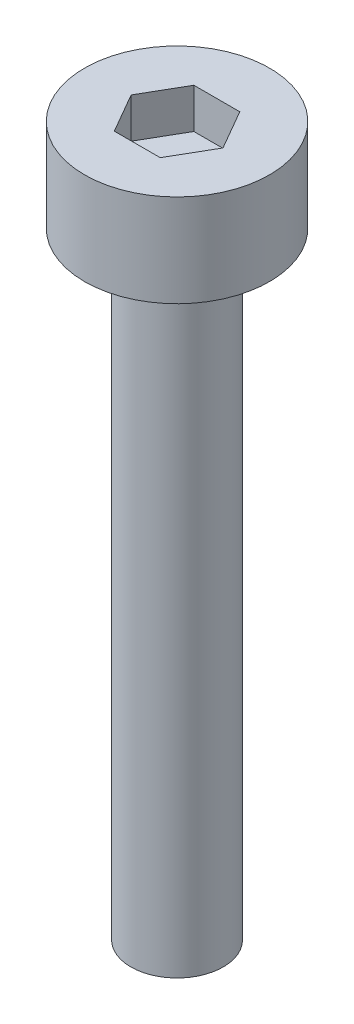
SolidWorks part; units mm, degrees
ref_plane "Front Plane" through (0, 0, 0) normal (0, 0, 1) x (1, 0, 0)
ref_plane "Top Plane" through (0, 0, 0) normal (0, 1, 0) x (1, 0, 0)
ref_plane "Right Plane" through (0, 0, 0) normal (1, 0, 0) x (0, 0, -1)
sketch "Sketch1" plane through (0, 0, 0) normal (0, 1, 0) x (1, 0, 0)
  circle A0 centre (0, 0) radius 1.5
  dimension "D1" = 3
extrude "ScrewShaft" add sketch "Sketch1" along normal blind 20
sketch "Sketch2" plane through (0, 20, 0) normal (0, 1, 0) x (1, 0, 0)
  circle A0 centre (0, 0) radius 3
  dimension "D1" = 6
extrude "Boss-Extrude2" add sketch "Sketch2" along normal blind 3
sketch "Sketch3" plane through (0, 23, 0) normal (0, 1, 0) x (1, 0, 0)
  line L0 (0, 0) -> (0, 1.29) construction
  line L1 (1.4896, 0) -> (0.7448, 1.29)
  line L2 (0.7448, 1.29) -> (-0.7448, 1.29)
  line L3 (-0.7448, 1.29) -> (-1.4896, 0)
  line L4 (-1.4896, 0) -> (-0.7448, -1.29)
  line L5 (-0.7448, -1.29) -> (0.7448, -1.29)
  line L6 (0.7448, -1.29) -> (1.4896, 0)
  circle A0 centre (0, 0) radius 1.29 construction
  dimension "D1" = 2.58
extrude "Cut-Extrude1" cut sketch "Sketch3" against normal blind 1.3
equation "\"X-ROD-SPACING\"=45"
equation "\"Y-ROD-SPACING\"=75"
equation "\"Z-ROD-SPACING\"=17.5"
equation "\"Y-BED-OFFSET\"=2"
equation "\"Y-BED-ROD-INSET\"=3.5"
equation "\"T-SLOT-NUT-FILLET-RADIUS\"=0.25"
equation "\"T-SLOT-SCREW-SHAFT-RADIUS\"=1.75"
equation "\"T-SLOT-SCREW-SHAFT-CUTOUT-LENGTH\"=10.5"
equation "\"T-SLOT-NUT-DEPTH\"=4.2"
equation "\"T-SLOT-NUT-WIDTH\"=3"
equation "\"T-SLOT-NUT-END-DISTANCE\"=8"
equation "\"ACRYLIC-THICKNESS\"=10"
equation "\"ACRYLIC-THICKNESS2\"=4.5"
equation "\"ACRYLIC-TAB-CUTOUT-SIZE\"=\"ACRYLIC-THICKNESS\"+\"ACRYLIC-TAB-TOLERANCE\"*2"
equation "\"ACRYLIC-TAB-WIDTH\"=\"ACRYLIC-THICKNESS\""
equation "\"ACRYLIC-M3-HOLE\"=3.1"
equation "\"SMOOTHROD-CAP-SCREW-DISTANCE\"=20"
equation "\"FRAME-WIDTH-INNER\"=370"
equation "\"NEMA17-HOLE-SPACING\"=31"
equation "\"NEMA17-CENTRAL-CUTOUT\"=22.5"
equation "\"Z-BRACKET-REACH\"=55"
equation "\"TOP-BRACKET-SPACING\"=40"
equation "\"SMOOTHROD-X-LENGTH\"=350"
equation "\"SMOOTHROD-Y-LENGTH\"=350"
equation "\"SMOOTHROD-Z-LENGTH\"=350"
equation "\"SMOOTHROD-TIGHTENING-HEADROOM\"=1"
equation "\"LEADSCREW-Z-LENGTH\"=300"
equation "\"SCREW-LENGTH-FRAME\"=\"ACRYLIC-THICKNESS\" + 10"
equation "\"SCREW-HEAD-RADIUS\"=6"
equation "\"PRINTED-X-SMOOTHROD-DIAMETER\"=8.2"
equation "\"PRINTED-X-SMOOTHROD-CUTOUT\"=10"
equation "\"PRINTED-X-BASE-HEIGHT\"=10"
equation "\"PRINTED-LM8UU-CUTOUT-SIZE\"=15.25"
equation "\"PRINTED-LM8UU-CUTOUT-LENGTH\"=24.5"
equation "\"PRINTED-X-IDLER-HEIGHT\"=16"
equation "\"PSU-MOUNTING-WIDTH\"=95"
equation "\"PSU-MOUNTING-HEIGHT\"=177"
equation "\"D1@ScrewShaft\"=\"SCREW-LENGTH-FRAME\""
equation "\"D1@Sketch2\"=\"SCREW-HEAD-RADIUS\""
